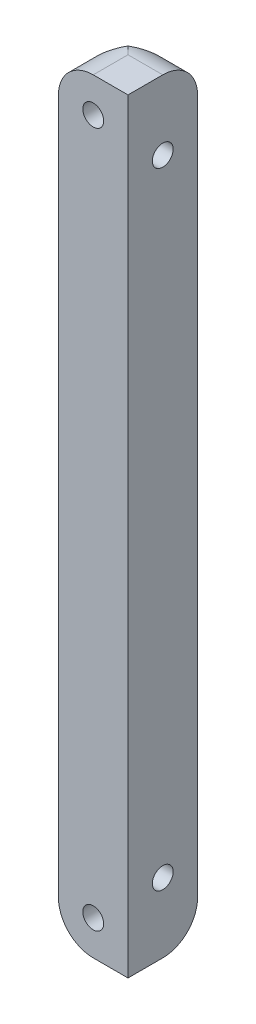
SolidWorks part; units mm, degrees
ref_plane "Front Plane" through (0, 0, 0) normal (0, 0, 1) x (1, 0, 0)
ref_plane "Top Plane" through (0, 0, 0) normal (0, 1, 0) x (1, 0, 0)
ref_plane "Right Plane" through (0, 0, 0) normal (1, 0, 0) x (0, 0, -1)
sketch "Sketch1" plane through (0, 0, 0) normal (0, 0, 1) x (1, 0, 0)
  line L1 (0, 0) -> (12.7, 0)
  line L2 (0, 0) -> (0, 139.7)
  line L3 (0, 139.7) -> (12.7, 139.7)
  line L4 (12.7, 0) -> (12.7, 139.7)
  dimension "D1" = 12.7
  dimension "D2" = 139.7
extrude "Boss-Extrude1" add sketch "Sketch1" along normal blind 12.7
chamfer "Chamfer1" distance 9.525 angle 45 1 edges at (0, 69.85, 0)
sketch "Sketch2" plane through (0, 0, 12.7) normal (0, 0, 1) x (1, 0, 0)
  line L0 (0, 139.7) -> (0, 0) construction
  line L1 (12.7, 139.7) -> (0, 139.7) construction
  line L2 (0, 0) -> (12.7, 0) construction
  circle A0 centre (6.35, 133.35) radius 1.905
  circle A1 centre (6.35, 6.35) radius 1.905
  point P10 (0, 0)
  dimension "D1" = 3.81
  dimension "D2" = 6.35
  dimension "D3" = 6.35
  dimension "D4" = 6.35
extrude "Cut-Extrude1" cut sketch "Sketch2" against normal through all
sketch "Sketch3" plane through (12.7, 0, 0) normal (1, 0, 0) x (0, 0, -1)
  line L0 (-12.7, 0) -> (0, 0) construction
  line L1 (-12.7, 139.7) -> (0, 139.7) construction
  line L2 (0, 0) -> (0, 139.7) construction
  circle A0 centre (-6.35, 127) radius 1.905
  circle A1 centre (-6.35, 12.7) radius 1.905
  point P10 (0, 0)
  dimension "D4" = 3.81
  dimension "D1" = 12.7
  dimension "D2" = 12.7
  dimension "D3" = 6.35
extrude "Cut-Extrude2" cut sketch "Sketch3" against normal through all
fillet "Fillet1" radius 6.35 4 edges at (11.1125, 139.7, 0) (0, 139.7, 11.1125) (0, 0, 11.1125) (11.1125, 0, 0)
